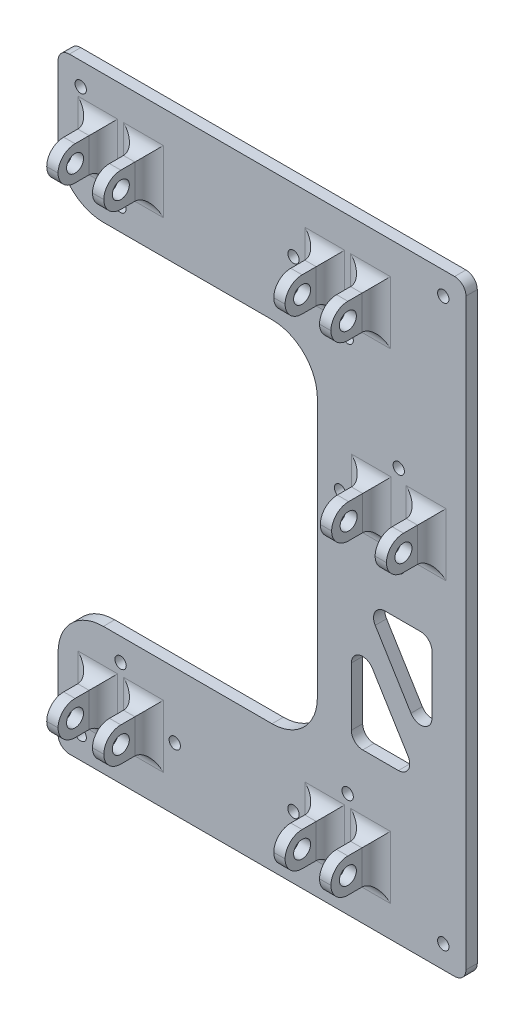
SolidWorks part; units mm, degrees
other "Markup3"
sketch "Sketch7" plane through (228.6, -342.9, 31.75) normal (0.076, -0.0024, 0.9971) x (0.9961, 0.0458, -0.0758)
other "Markup4"
sketch "Sketch8" plane through (228.6, -342.9, 31.75) normal (0.076, -0.0024, 0.9971) x (0.9961, 0.0458, -0.0758)
material "7075-T6 (SN)"
ref_plane "Front Plane" through (0, 0, 0) normal (0, 0, 1) x (1, 0, 0)
ref_plane "Top Plane" through (0, 0, 0) normal (0, 1, 0) x (1, 0, 0)
ref_plane "Right Plane" through (0, 0, 0) normal (1, 0, 0) x (0, 0, -1)
sketch "Sketch1" plane through (0, 0, 0) normal (0, 0, 1) x (1, 0, 0)
  line L1 (0, 0) -> (228.6, 0)
  line L2 (0, 0) -> (0, -339.725)
  line L3 (0, -339.725) -> (228.6, -339.725)
  line L4 (228.6, 0) -> (228.6, -339.725)
  dimension "D1" = 339.725
  dimension "D2" = 228.6
extrude "Boss-Extrude1" add sketch "Sketch1" along normal blind 6.35
sketch "Sketch2" plane through (0, 0, 6.35) normal (0, 0, 1) x (1, 0, 0)
  line L0 (0, 0) -> (0, -339.725) construction
  line L1 (25.4, -26.035) -> (44.704, -26.035)
  line L2 (25.4, -26.035) -> (25.4, -45.085)
  line L3 (25.4, -45.085) -> (44.704, -45.085)
  line L4 (44.704, -26.035) -> (44.704, -45.085)
  line L5 (152.654, -26.035) -> (171.958, -26.035)
  line L6 (152.654, -26.035) -> (152.654, -45.085)
  line L7 (152.654, -45.085) -> (171.958, -45.085)
  line L8 (171.958, -26.035) -> (171.958, -45.085)
  line L9 (25.4, -295.275) -> (44.704, -295.275)
  line L10 (25.4, -295.275) -> (25.4, -314.325)
  line L11 (25.4, -314.325) -> (44.704, -314.325)
  line L12 (44.704, -295.275) -> (44.704, -314.325)
  line L13 (152.654, -295.275) -> (171.958, -295.275)
  line L14 (152.654, -295.275) -> (152.654, -314.325)
  line L15 (152.654, -314.325) -> (171.958, -314.325)
  line L16 (171.958, -295.275) -> (171.958, -314.325)
  line L18 (0, -339.725) -> (228.6, -339.725) construction
  line L19 (171.958, -304.8) -> (178.728, -304.8) construction
  line L20 (178.728, -304.8) -> (178.728, -132.588) construction
  line L21 (178.728, -123.063) -> (172.378, -123.063)
  line L22 (178.728, -123.063) -> (203.112, -123.063)
  line L23 (178.728, -123.063) -> (178.728, -142.113)
  line L24 (178.728, -142.113) -> (203.112, -142.113)
  line L25 (203.112, -123.063) -> (203.112, -142.113)
  line L26 (152.654, -26.035) -> (146.304, -26.035)
  line L27 (152.654, -26.035) -> (152.654, -45.085)
  line L28 (152.654, -45.085) -> (146.304, -45.085)
  line L29 (146.304, -26.035) -> (146.304, -45.085)
  line L30 (171.958, -26.035) -> (178.308, -26.035)
  line L31 (171.958, -26.035) -> (171.958, -45.085)
  line L32 (171.958, -45.085) -> (178.308, -45.085)
  line L33 (178.308, -26.035) -> (178.308, -45.085)
  line L34 (44.704, -26.035) -> (51.054, -26.035)
  line L35 (44.704, -26.035) -> (44.704, -45.085)
  line L36 (44.704, -45.085) -> (51.054, -45.085)
  line L37 (51.054, -26.035) -> (51.054, -45.085)
  line L38 (25.4, -26.035) -> (19.05, -26.035)
  line L39 (25.4, -26.035) -> (25.4, -45.085)
  line L40 (25.4, -45.085) -> (19.05, -45.085)
  line L41 (19.05, -26.035) -> (19.05, -45.085)
  line L42 (44.704, -295.275) -> (51.054, -295.275)
  line L43 (44.704, -295.275) -> (44.704, -314.325)
  line L44 (44.704, -314.325) -> (51.054, -314.325)
  line L45 (51.054, -295.275) -> (51.054, -314.325)
  line L46 (25.4, -295.275) -> (19.05, -295.275)
  line L47 (25.4, -295.275) -> (25.4, -314.325)
  line L48 (25.4, -314.325) -> (19.05, -314.325)
  line L49 (19.05, -295.275) -> (19.05, -314.325)
  line L50 (171.958, -295.275) -> (178.308, -295.275)
  line L51 (171.958, -295.275) -> (171.958, -314.325)
  line L52 (171.958, -314.325) -> (178.308, -314.325)
  line L53 (178.308, -295.275) -> (178.308, -314.325)
  line L54 (152.654, -295.275) -> (146.304, -295.275)
  line L55 (152.654, -295.275) -> (152.654, -314.325)
  line L56 (152.654, -314.325) -> (146.304, -314.325)
  line L57 (146.304, -295.275) -> (146.304, -314.325)
  line L58 (178.728, -123.063) -> (178.728, -142.113)
  line L59 (178.728, -142.113) -> (172.378, -142.113)
  line L60 (172.378, -123.063) -> (172.378, -142.113)
  line L61 (203.112, -123.063) -> (209.462, -123.063)
  line L62 (203.112, -123.063) -> (203.112, -142.113)
  line L63 (203.112, -142.113) -> (209.462, -142.113)
  line L64 (209.462, -123.063) -> (209.462, -142.113)
  point P18 (152.654, -304.8)
  point P21 (19.05, -35.56)
  point P29 (178.728, -132.588)
  point P60 (19.05, -304.8)
  dimension "D1" = 19.05
  dimension "D2" = 19.304
  dimension "D3" = 19.05
  dimension "D4" = 19.304
  dimension "D5" = 19.05
  dimension "D6" = 19.304
  dimension "D7" = 19.05
  dimension "D8" = 19.304
  dimension "D9" = 107.95
  dimension "D10" = 25.4
  dimension "D11" = 107.95
  dimension "D12" = 25.4
  dimension "D13" = 269.24
  dimension "D14" = 172.212
  dimension "D15" = 6.77
  dimension "D16" = 19.05
  dimension "D17" = 24.384
  dimension "D18" = 19.05
  dimension "D19" = 6.35
  dimension "D20" = 19.05
  dimension "D21" = 6.35
  dimension "D22" = 19.05
  dimension "D23" = 19.05
  dimension "0.25" = 6.35
  dimension "D24" = 19.05
  dimension "D25" = 6.35
  dimension "D26" = 6.35
  dimension "D27" = 19.05
  dimension "D28" = 6.35
  dimension "D29" = 19.05
  dimension "D30" = 6.35
  dimension "D31" = 19.05
  dimension "D32" = 6.35
  dimension "D33" = 19.05
  dimension "D34" = 6.35
  dimension "D35" = 19.05
  dimension "D36" = 6.35
extrude "Boss-Extrude2" add sketch "Sketch2" along normal blind 25.4 contours L38 L41 L40 L2 | L37 L34 L4 L36 | L26 L29 L28 L6 | L33 L30 L8 L32 | L21 L60 L59 L23 | L64 L61 L25 L63 | L53 L50 L16 L52 | L54 L57 L56 L14 | L46 L49 L48 L10 | L45 L42 L12 L44 region at (22.225, -35.56, 6.35) region at (47.879, -35.56, 6.35) region at (149.479, -35.56, 6.35) region at (175.133, -35.56, 6.35) region at (22.225, -304.8, 6.35) region at (47.879, -304.8, 6.35) region at (149.479, -304.8, 6.35) region at (175.133, -304.8, 6.35) region at (175.553, -132.588, 6.35) region at (206.287, -132.588, 6.35)
fillet "Fillet1" radius 9.525 20 edges at (22.225, -314.325, 31.75) (22.225, -295.275, 31.75) (47.879, -314.325, 31.75) (47.879, -295.275, 31.75) (149.479, -314.325, 31.75) (149.479, -295.275, 31.75) (175.133, -314.325, 31.75) (175.133, -295.275, 31.75) (206.287, -142.113, 31.75) (206.287, -123.063, 31.75) (175.553, -142.113, 31.75) (175.553, -123.063, 31.75) (175.133, -45.085, 31.75) (175.133, -26.035, 31.75) (149.479, -45.085, 31.75) (149.479, -26.035, 31.75) (47.879, -45.085, 31.75) (47.879, -26.035, 31.75) (22.225, -45.085, 31.75) (22.225, -26.035, 31.75)
fillet "Fillet2" radius 8 40 edges at (175.133, -314.325, 6.35) (178.308, -304.8, 6.35) (175.133, -295.275, 6.35) (149.479, -295.275, 6.35) (149.479, -314.325, 6.35) (146.304, -304.8, 6.35) (51.054, -304.8, 6.35) (47.879, -295.275, 6.35) (22.225, -295.275, 6.35) (47.879, -314.325, 6.35) (22.225, -314.325, 6.35) (19.05, -304.8, 6.35) (22.225, -45.085, 6.35) (19.05, -35.56, 6.35) (22.225, -26.035, 6.35) (47.879, -26.035, 6.35) (47.879, -45.085, 6.35) (51.054, -35.56, 6.35) (206.287, -123.063, 6.35) (209.462, -132.588, 6.35) (206.287, -142.113, 6.35) (175.553, -123.063, 6.35) (172.378, -132.588, 6.35) (175.553, -142.113, 6.35) (149.479, -26.035, 6.35) (175.133, -26.035, 6.35) (178.308, -35.56, 6.35) (175.133, -45.085, 6.35) (149.479, -45.085, 6.35) (146.304, -35.56, 6.35) (44.704, -304.8, 6.35) (25.4, -304.8, 6.35) (152.654, -304.8, 6.35) (171.958, -304.8, 6.35) (203.112, -132.588, 6.35) (171.958, -35.56, 6.35) (152.654, -35.56, 6.35) (25.4, -35.56, 6.35) (44.704, -35.56, 6.35) (178.728, -132.588, 6.35)
sketch "Sketch3" plane through (19.05, 0, 0) normal (-1, 0, 0) x (0, 0, 1)
  line L0 (22.225, -26.035) -> (22.225, -45.085) construction
  line L1 (22.225, -123.063) -> (22.225, -142.113) construction
  line L2 (22.225, -295.275) -> (22.225, -314.325) construction
  circle A0 centre (22.225, -35.56) radius 4.7625
  circle A1 centre (22.225, -132.588) radius 4.7625
  arc A2 (22.225, -314.325) -> (31.75, -304.8) centre (22.225, -304.8) ccw construction
  circle A3 centre (22.225, -304.8) radius 4.7625
extrude "Cut-Extrude1" cut sketch "Sketch3" against normal through all
sketch "Sketch5" plane through (0, 0, 6.35) normal (0, 0, 1) x (1, 0, 0)
  line L0 (228.6, 0) -> (0, 0) construction
  line L1 (0, 0) -> (0, -339.725) construction
  line L2 (228.6, -339.725) -> (228.6, 0) construction
  line L3 (138.304, -53.085) -> (138.304, -18.035) construction
  line L4 (138.304, -53.085) -> (138.304, -18.035)
  line L5 (138.304, -53.085) -> (186.308, -53.085) construction
  line L6 (138.304, -35.56) -> (59.054, -35.56) construction
  line L7 (59.054, -18.035) -> (59.054, -53.085) construction
  line L8 (162.306, -53.085) -> (162.306, -77.4398) construction
  line L9 (10.796, -53.085) -> (59.054, -53.085) construction
  line L10 (33.4, -53.085) -> (11.05, -53.085) construction
  line L11 (34.925, -53.085) -> (34.925, -74.5657) construction
  line L12 (186.728, -115.063) -> (195.112, -115.063) construction
  line L13 (195.112, -115.063) -> (190.92, -115.063) construction
  line L14 (190.92, -115.063) -> (190.92, -77.4398) construction
  line L15 (190.92, -77.4398) -> (190.92, -189.3922) construction
  line L16 (164.378, -150.113) -> (164.378, -115.063) construction
  line L17 (217.462, -150.113) -> (195.112, -150.113) construction
  line L18 (160.654, -287.275) -> (163.958, -287.275) construction
  line L19 (33.4, -287.275) -> (36.704, -287.275) construction
  line L20 (36.704, -287.275) -> (35.052, -287.275) construction
  line L21 (35.052, -287.275) -> (35.052, -271.8353) construction
  line L22 (162.306, -287.275) -> (162.306, -271.8353) construction
  line L23 (59.054, -304.8) -> (138.304, -304.8) construction
  line L24 (59.054, -287.275) -> (59.054, -322.325) construction
  line L25 (138.304, -322.325) -> (138.304, -287.275) construction
  line L26 (0, -339.725) -> (228.6, -339.725) construction
  circle A0 centre (12.7, -12.7) radius 3.175
  circle A1 centre (215.9, -12.7) radius 3.175
  circle A2 centre (65.404, -35.56) radius 3.175
  circle A3 centre (131.954, -35.56) radius 3.175
  circle A4 centre (162.306, -59.435) radius 3.175
  circle A5 centre (34.925, -59.435) radius 3.175
  circle A6 centre (190.92, -108.713) radius 3.175
  circle A7 centre (158.028, -136.1329) radius 3.175
  circle A8 centre (190.92, -156.463) radius 3.175
  circle A9 centre (35.052, -280.925) radius 3.175
  circle A10 centre (65.404, -304.8) radius 3.175
  circle A11 centre (12.7, -327.025) radius 3.175
  circle A12 centre (215.9, -327.025) radius 3.175
  circle A13 centre (131.954, -304.8) radius 3.175
  circle A14 centre (162.306, -280.925) radius 3.175
  dimension "D1" = 12.7
  dimension "D3" = 12.7
  dimension "D5" = 6.35
  dimension "D6" = 6.35
  dimension "D7" = 6.35
  dimension "D8" = 6.35
  dimension "D9" = 6.35
  dimension "D10" = 6.35
  dimension "D11" = 6.35
  dimension "D12" = 6.35
  dimension "D13" = 6.35
  dimension "D14" = 6.35
  dimension "D15" = 6.35
  dimension "D17" = 12.7
  dimension "D18" = 12.7
  dimension "D19" = 12.7
  dimension "D2" = 12.7
  dimension "D4" = 12.7
  dimension "D16" = 12.7
extrude "Cut-Extrude2" cut sketch "Sketch5" against normal through all contours A0 | A5 | A3 | A1 | A4 | A6 | A7 | A8 | A12 | A14 | A13 | A10 | A9 | A11 region at (12.7, -12.7, 6.35) region at (215.9, -12.7, 6.35) region at (131.954, -35.56, 6.35) region at (162.306, -59.435, 6.35) region at (34.925, -59.435, 6.35) region at (190.92, -108.713, 6.35) region at (158.028, -136.1329, 6.35) region at (190.92, -156.463, 6.35) region at (35.052, -280.925, 6.35) region at (65.404, -304.8, 6.35) region at (12.7, -327.025, 6.35) region at (215.9, -327.025, 6.35) region at (131.954, -304.8, 6.35) region at (162.306, -280.925, 6.35)
sketch "Sketch9" plane through (0, 0, 6.35) normal (0, 0, 1) x (1, 0, 0)
  line L0 (0, 0) -> (0, -339.725) construction
  line L1 (0, -72.135) -> (145.328, -72.135)
  line L2 (0, -72.135) -> (0, -268.225)
  line L3 (0, -268.225) -> (145.328, -268.225)
  line L4 (145.328, -72.135) -> (145.328, -268.225)
  line L5 (228.6, -339.725) -> (228.6, 0) construction
  line L6 (164.378, -181.863) -> (209.55, -181.863)
  line L7 (164.378, -181.863) -> (164.378, -255.525)
  line L8 (164.378, -255.525) -> (209.55, -255.525)
  line L9 (209.55, -181.863) -> (209.55, -255.525)
  line L10 (164.378, -181.863) -> (209.55, -255.525)
  line L11 (171.8269, -181.863) -> (209.55, -243.3781)
  line L12 (164.378, -194.0099) -> (202.1011, -255.525)
  line L14 (158.9648, -185.1826) -> (204.1368, -258.8446) construction
  line L15 (169.7912, -178.5434) -> (214.9632, -252.2054) construction
  circle A0 centre (34.925, -59.435) radius 3.175 construction
  circle A1 centre (35.052, -280.925) radius 3.175 construction
  circle A2 centre (158.028, -136.1329) radius 3.175 construction
  circle A3 centre (162.306, -280.925) radius 3.175 construction
  circle A4 centre (190.92, -156.463) radius 3.175 construction
  dimension "D1" = 12.7
  dimension "D3" = 12.7
  dimension "D4" = 25.4
  dimension "D7" = 25.4
  dimension "D2" = 12.7
  dimension "D5" = 19.05
  dimension "D6" = 19.05
  dimension "D8" = 6.35
  dimension "D9" = 6.35
extrude "Cut-Extrude3" cut sketch "Sketch9" against normal through all contours L4 L1 L2 L3 | L12 L7 L8 | L6 L11 L9 region at (72.664, -170.18, 6.35) region at (196.9756, -202.368, 6.35) region at (176.9524, -235.02, 6.35)
fillet "Fillet3" radius 25.4 4 edges at (0, -268.225, 3.175) (145.328, -268.225, 3.175) (145.328, -72.135, 3.175) (0, -72.135, 3.175)
fillet "Fillet4" radius 6.35 10 edges at (228.6, -339.725, 3.175) (0, -339.725, 3.175) (0, 0, 3.175) (228.6, 0, 3.175) (171.8269, -181.863, 3.175) (209.55, -181.863, 3.175) (209.55, -243.3781, 3.175) (164.378, -194.0099, 3.175) (202.1011, -255.525, 3.175) (164.378, -255.525, 3.175)
move or copy body "Body-Move/Copy2" [suppressed] bodies to move or copy 105
move or copy body "Body-Move/Copy1" [suppressed] bodies to move or copy 105
